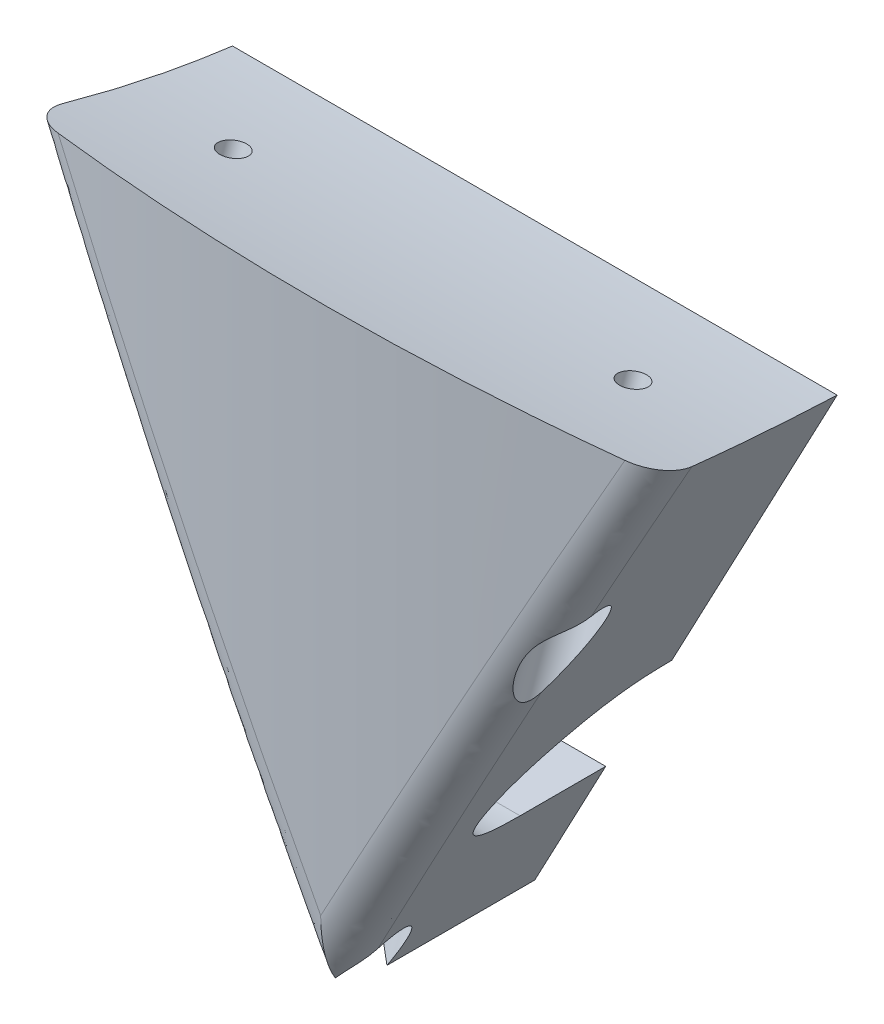
SolidWorks part; units mm, degrees
ref_plane "Front Plane" through (0, 0, 0) normal (0, 0, 1) x (1, 0, 0)
ref_plane "Top Plane" through (0, 0, 0) normal (0, 1, 0) x (1, 0, 0)
ref_plane "Right Plane" through (0, 0, 0) normal (1, 0, 0) x (0, 0, -1)
sketch "Sketch1" plane through (0, 0, 0) normal (0, 0, 1) x (1, 0, 0)
  line L0 (-57.15, 0) -> (0, -107.95)
  line L1 (0, -107.95) -> (57.15, 0)
  line L2 (57.15, 0) -> (-57.15, 0)
  point P3 (0, 0)
  dimension "D1" = 114.3
  dimension "D2" = 107.95
extrude "Boss-Extrude1" add sketch "Sketch1" along normal blind 38.1
sketch "Sketch3" plane through (0, 0, 0) normal (0, 1, 0) x (1, 0, 0)
  line L0 (-57.15, -38.1) -> (-57.15, 0) construction
  line L1 (57.15, -38.1) -> (57.15, 0) construction
  line L2 (57.15, -38.1) -> (-57.15, -38.1) construction
  line L3 (57.15, -38.1) -> (57.15, -33.3375)
  line L4 (-57.15, -38.1) -> (-57.15, -33.3375)
  line L5 (57.15, -38.1) -> (-57.15, -38.1)
  arc A0 (-57.15, -33.3375) -> (57.15, -33.3375) centre (0, 307.1812) ccw
  line M2 (-57.15, 0) -> (-57.15, -38.1)
  line M3 (-57.15, -38.1) -> (57.15, -38.1)
  line M4 (57.15, -38.1) -> (57.15, 0)
  dimension "D1" = 4.7625
extrude "Cut-Extrude2" cut sketch "Sketch3" against normal through all contours A0 M2 M3 | A0 L5 M4
sketch "Sketch2" plane through (0, 0, 0) normal (1, 0, 0) x (0, 0, -1)
  line L0 (0, -61.9125) -> (-38.1, -61.9125) construction
  line L1 (0, -107.95) -> (0, 0) construction
  line L2 (0, -6.35) -> (-38.0863, -3.0179) construction
  line L3 (-33.3375, 0) -> (0, 0) construction
  line L4 (0, -84.1375) -> (-15.2318, -84.1375)
  line L5 (0, -61.9125) -> (0, -84.1375)
  line L6 (0, -6.35) -> (-38.1, -6.35) construction
  line L8 (0, 0) -> (0, -6.35)
  line L9 (-33.3375, 0) -> (-38.1, 0) construction
  line L10 (-38.1, 0) -> (-38.1, -107.95) construction
  line L11 (-38.1, 0) -> (0, 0)
  line L12 (-38.1, 0) -> (-38.1, -6.35) construction
  arc A0 (-38.1, 0) -> (0, -6.35) centre (21.6342, 240.9304) ccw
  spline S0 degree 3 poles (0, -61.9125) (-7.2306, -61.9125) (-13.7613, -64.6538) (-21.9301, -71.1391) (-27.0214, -78.8571) (-25.502, -84.1375) (-15.2318, -84.1375) knots 0 0 0 0 0.395555 0.572611 0.713837 1 1 1 1
  point P4 (-38.1, -3.175)
  dimension "D3" = 6.35
  dimension "D1" = 61.9125
  dimension "D2" = 22.225
  dimension "D4" = 5
extrude "Cut-Extrude1" cut sketch "Sketch2" against normal through all both and the other way through all
fillet "Fillet1" radius 6.35 2 edges at (-28.3775, -54.348, 36.9319) (28.3775, -54.348, 36.9319)
ref_plane "Plane1" through (0, -13.5552, 4.9337) normal (0, 0.9397, -0.342) x (1, 0, 0)
sketch "Sketch4" plane through (0, -13.5552, 4.9337) normal (0, 0.9397, -0.342) x (1, 0, 0)
  line L0 (0, 0) -> (0, -50000) construction
  line L1 (0, -15.6082) -> (56.9699, -15.6082) construction
  line L2 (-53.7882, 2.1718) -> (53.7882, 2.1718) construction
  circle A0 centre (-35.56, -15.6082) radius 4.7625
  circle A1 centre (35.56, -15.6082) radius 4.7625
  dimension "D1" = 9.525
  dimension "D2" = 35.56
  dimension "D3" = 17.78
extrude "Cut-Extrude3" cut sketch "Sketch4" against normal through all
sketch "Sketch6" plane through (0, -13.5552, 4.9337) normal (0, 0.9397, -0.342) x (1, 0, 0)
  line L0 (0, 0) -> (0, -50000) construction
  circle A0 centre (-35.56, -15.6082) radius 2.3812
  circle A1 centre (35.56, -15.6082) radius 4.7625
  circle A2 centre (35.56, -15.6082) radius 4.7625 construction
  circle A3 centre (-35.56, -15.6082) radius 4.7625
  circle A4 centre (-35.56, -15.6082) radius 4.7625 construction
  circle A5 centre (35.56, -15.6082) radius 2.3812
  dimension "D3" = 4.7625
  dimension "D1" = 0
  dimension "D2" = 0
extrude "Cut-Extrude4" cut sketch "Sketch6" against normal through all both and the other way through all
sketch "Sketch8" plane through (0, 0, 0) normal (1, 0, 0) x (0, 0, -1)
  line L0 (-15.2318, -84.1375) -> (49984.7682, -84.1375) construction
  line L1 (-17.1665, -85.0981) -> (-25.1077, -82.2077) construction
  line L2 (-22.3744, -83.2025) -> (17078.6327, 46901.4285)
  spline S0 degree 3 poles (1887.2222, -723.8184) (61.4858, -102.1573) (21.023, -37.0378) (-21.9301, -71.1391) (-39.4511, -97.699) (46.0193, -118.4925) (1835.7757, 671.8161) knots -3.039676 -3.039676 -3.039676 -3.039676 0.395555 0.572611 0.713837 2.475632 2.475632 2.475632 2.475632 only from (0, -61.9125) to (-15.2318, -84.1375) construction
  spline S1 degree 3 poles (0, -61.9125) (-7.2306, -61.9125) (-13.7613, -64.6538) (-21.9301, -71.1391) (-27.0214, -78.8571) (-25.502, -84.1375) (-15.2318, -84.1375) knots 0 0 0 0 0.395555 0.572611 0.713837 1 1 1 1
  point P2 (-22.3744, -83.2025)
  dimension "D1" = 20
ref_plane "Plane2" through (0, -80.6607, 29.3581) normal (0, 0.9397, -0.342) x (1, 0, 0)
sketch "Sketch11" plane through (0, -80.6607, 29.3581) normal (0, 0.9397, -0.342) x (1, 0, 0)
  circle A0 centre (0, 7.4318) radius 2.3813
  point P0 (0, 7.4318)
  dimension "D1" = 4.7625
extrude "Cut-Extrude5" cut sketch "Sketch11" against normal through all and the other way up to next
sketch "Sketch12" plane through (0, -80.6607, 29.3581) normal (0, 0.9397, -0.342) x (1, 0, 0)
  circle A0 centre (0, 7.4318) radius 4.7625
  point P0 (0, 7.4318)
  dimension "D1" = 9.525
extrude "Cut-Extrude6" cut sketch "Sketch12" against normal through all from offset 6.35
